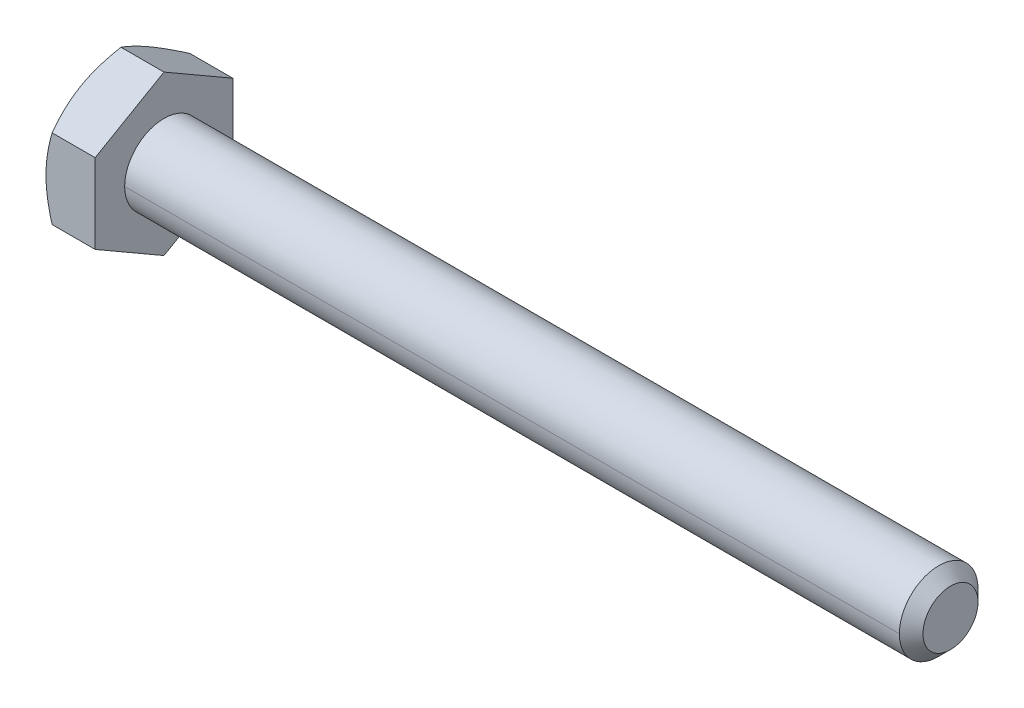
SolidWorks part; units mm, degrees
material "Alloy Steel"
ref_plane "Front Plane" through (0, 0, 0) normal (0, 0, 1) x (1, 0, 0)
ref_plane "Top Plane" through (0, 0, 0) normal (0, 1, 0) x (1, 0, 0)
ref_plane "Right Plane" through (0, 0, 0) normal (1, 0, 0) x (0, 0, -1)
sketch "Sketch1" plane through (0, 0, 0) normal (0, 0, 1) x (1, 0, 0)
  line L0 (-33.7344, 0) -> (33.7344, 0) construction
  line L1 (33.7344, 3.175) -> (33.7344, -3.175) construction
  line L2 (-29.7656, 5.5562) -> (-29.7656, -5.5562) construction
  line L3 (-33.7344, 5.5562) -> (-33.7344, -5.5562) construction
  point P9 (-29.7656, 0)
  point P10 (29.2894, -3.175)
  dimension "D1" = 4.445
  dimension "Screw Dia" = 6.35
  dimension "Hex" = 11.1125
  dimension "Head Ht" = 3.9688
  dimension "Screw Lenght" = 63.5
ref_plane "Plane2" through (33.7344, 0, 0) normal (1, 0, 0) x (0, 0, -1)
sketch "Sketch5" plane through (33.7344, 0, 0) normal (1, 0, 0) x (0, 0, -1)
  circle A0 centre (0, 0) radius 3.175
extrude "Boss-Extrude3" add sketch "Sketch5" against normal up to vertex (63.5 mm away) up to point (-29.7656, 0, 0)
sketch "Sketch9" plane through (33.7344, 0, 0) normal (1, 0, 0) x (0, 0, -1)
  circle A1 centre (0, 0) radius 3.175
  circle A2 centre (0, 0) radius 3.175
  dimension "D1" = 0
curve "Helix/Spiral1" [suppressed] pitch 1.27 height 20.32 turns 16 parameters "Pitch"=1.27
chamfer "Chamfer1" distance 0.9525 angle 45 1 edges at (33.7344, 0, -3.175)
sketch "Sketch10" plane through (0, 0, 0) normal (0, 0, 1) x (1, 0, 0)
  line L0 (33.7344, 3.175) -> (34.2106, 2.3501)
  line L1 (34.2106, 2.3501) -> (34.3694, 2.3501)
  line L2 (34.3694, 2.3501) -> (34.8456, 3.175)
  line L3 (33.7344, 3.175) -> (34.8456, 3.175)
  line L4 (34.29, 3.175) -> (34.29, 2.3501) construction
  line L5 (33.9725, 2.7626) -> (34.6075, 2.7626) construction
  dimension "D1" = 60
  dimension "D2" = 0.1588
  dimension "D3" = 0.635
sweep "Cut-Sweep1" [suppressed] cut profiles "Sketch10" path "Helix/Spiral1"
sketch "Sketch11" plane through (0, 0, 0) normal (0, 0, 1) x (1, 0, 0)
  line L0 (-29.7656, 3.175) -> (-29.7656, 0)
  line L1 (-29.7656, 0) -> (17.8594, 0)
  line L3 (17.8594, 0) -> (14.6844, 3.175)
  line L4 (-29.7656, 3.175) -> (14.6844, 3.175)
  dimension "D1" = 45
  dimension "MIn Thread" = 19.05
revolve "Revolve1" add sketch "Sketch11" angle 360 about L1
sketch "Sketch6" plane through (-29.7656, 0, 0) normal (-1, 0, 0) x (0, 0, 1)
  line L0 (0, 5.5562) -> (0, -5.5562) construction
  line L1 (5.5563, 3.2079) -> (0, 6.4158)
  line L2 (0, 6.4158) -> (-5.5562, 3.2079)
  line L3 (-5.5562, 3.2079) -> (-5.5562, -3.2079)
  line L4 (-5.5562, -3.2079) -> (0, -6.4158)
  line L5 (0, -6.4158) -> (5.5563, -3.2079)
  line L6 (5.5563, -3.2079) -> (5.5563, 3.2079)
  circle A0 centre (0, 0) radius 5.5563 construction
extrude "Boss-Extrude4" add sketch "Sketch6" along normal up to vertex (3.9688 mm away) up to point (-33.7344, -5.5562, 0)
sketch "Sketch7" plane through (-33.7344, 0, 0) normal (-1, 0, 0) x (0, 0, 1)
  circle A0 centre (0, 0) radius 5.5563 construction
  circle A1 centre (0, 0) radius 5.5563
sketch "Sketch8" plane through (-33.7344, 0, 0) normal (-1, 0, 0) x (0, 0, 1)
  circle A0 centre (0, 0) radius 5.5563 construction
  circle A1 centre (0, 0) radius 5.5563
extrude "Cut-Extrude3" cut sketch "Sketch8" against normal through all draft 60 flip side to cut
sketch "Sketch12" plane through (-33.7344, 0, 0) normal (-1, 0, 0) x (0, 0, 1)
  line L0 (0, 4.2783) -> (0, 2.3892) construction
  line L1 (0.1667, 4.2783) -> (0.1667, 2.3892)
  line L2 (-0.1667, 4.2783) -> (-0.1667, 2.3892)
  line L3 (0, 3.175) -> (0, -3.175) construction
  arc A0 (0.1667, 4.2783) -> (-0.1667, 4.2783) centre (0, 4.2783) ccw
  arc A1 (-0.1667, 2.3892) -> (0.1667, 2.3892) centre (0, 2.3892) ccw
  circle A3 centre (0, 0) radius 2.2225 construction
  circle A4 centre (0, 0) radius 4.445 construction
  point P2 (0, 3.3337)
  dimension "D1" = 4.445
  dimension "D3" = 8.89
  dimension "D2" = 0.3334
extrude "Cut-Extrude4" cut sketch "Sketch12" against normal blind 0.254
pattern_circular "CirPattern1" count 3 over 360 about axis through (-29.7656, 0, 0) along (1, 0, 0) of "Cut-Extrude4"
split line "Split Line2"
equation "\"D2@Sketch10\" = \"Pitch@Helix/Spiral1\"*.125"
equation "\"D3@Sketch10\" = \"Pitch@Helix/Spiral1\"*.5"
equation "\"D3@Helix/Spiral1\" = \"MIn Thread@Sketch11\"+\"Pitch@Helix/Spiral1\""
equation "\"D1@Chamfer1\" = \"Pitch@Helix/Spiral1\"*.75"
equation "\"D1@Sketch12\" = \"Hex@Sketch1\"*.4"
equation "\"D3@Sketch12\" = \"Hex@Sketch1\"*.8"
equation "\"D2@Sketch12\" = \"Hex@Sketch1\"*.03"
equation "\"D1@Sketch1\" = \"Pitch@Helix/Spiral1\"*3.5"
